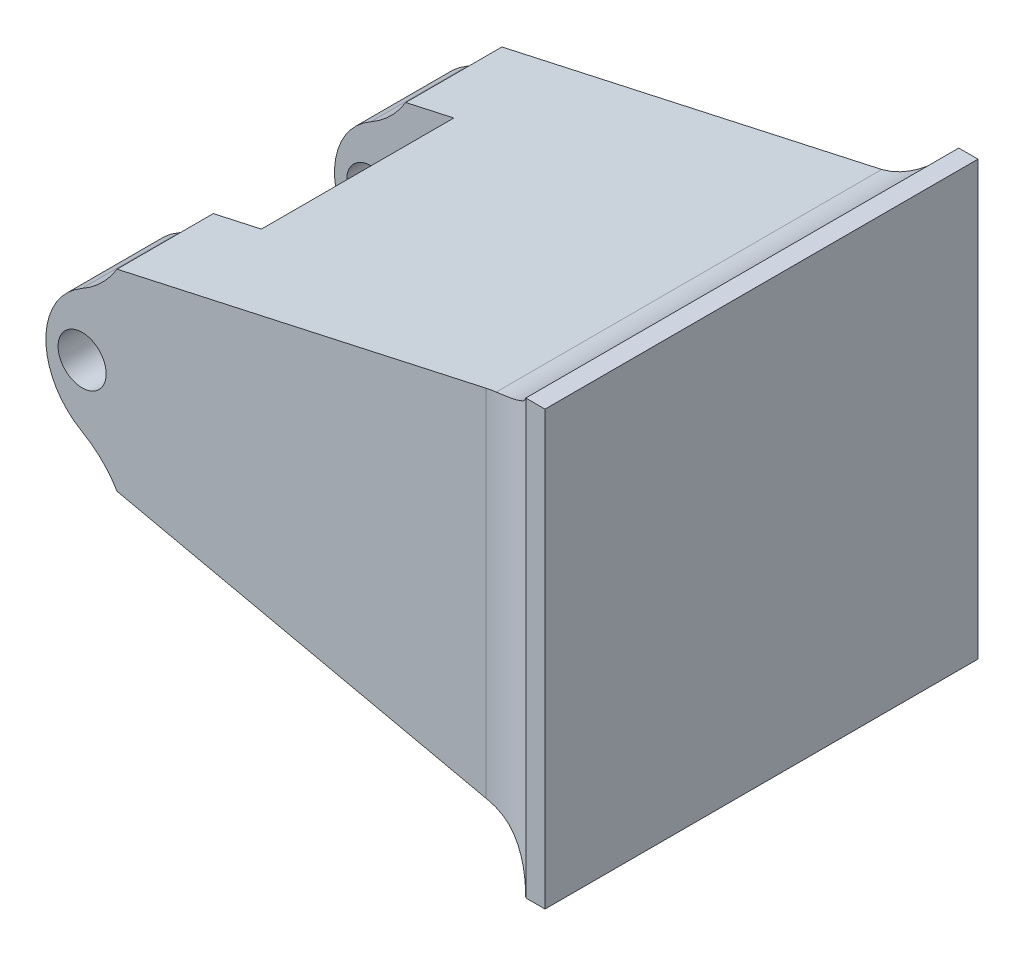
SolidWorks part; units mm, degrees
ref_plane "Front Plane" through (0, 0, 0) normal (0, 0, 1) x (1, 0, 0)
ref_plane "Top Plane" through (0, 0, 0) normal (0, 1, 0) x (1, 0, 0)
ref_plane "Right Plane" through (0, 0, 0) normal (1, 0, 0) x (0, 0, -1)
sketch "Sketch1" plane through (0, 0, 0) normal (0, 0, 1) x (1, 0, 0)
  line L0 (0, 0) -> (45.3393, -10)
  line L1 (45.3393, -10) -> (45.3393, 30)
  line L2 (0, 20) -> (45.3393, 30)
  line L3 (0, 0) -> (0, 20)
  dimension "D1" = 40
  dimension "D2" = 20
extrude "Boss-Extrude1" add sketch "Sketch1" along normal blind 20 and the other way blind 20 contours L2 L1 L0 L3
sketch "Sketch2" plane through (45.3393, 0, 0) normal (1, 0, 0) x (0, 0, -1)
  line L1 (-22.8606, 32.5) -> (22.1394, 32.5)
  line L2 (-22.8606, 32.5) -> (-22.8606, -12.5)
  line L3 (-22.8606, -12.5) -> (22.1394, -12.5)
  line L4 (22.1394, 32.5) -> (22.1394, -12.5)
  line L5 (-22.8606, 32.5) -> (22.1394, -12.5) construction
  line L6 (-22.8606, -12.5) -> (22.1394, 32.5) construction
  line L7 (20, 30) -> (-20, 30) construction
  point P0 (-0.3606, 10)
  dimension "D1" = 45
  dimension "D2" = 45
  dimension "D3" = 20
extrude "Boss-Extrude2" add sketch "Sketch2" along normal blind 2
sketch "Sketch3" plane through (0, 0, 20) normal (0, 0, 1) x (1, 0, 0)
  line L0 (0, 0) -> (0, 20) construction
  line L1 (0, 17.4004) -> (0, 2.5996)
  arc A0 (0, 17.4004) -> (0, 2.5996) centre (0, 10) ccw
  circle A2 centre (-3.6319, 10) radius 2.5
  dimension "D1" = 5
  dimension "D2" = 0
extrude "Boss-Extrude3" add sketch "Sketch3" against normal blind 10
fillet "Fillet1" radius 10 2 edges at (0, 2.5996, 15) (0, 17.4004, 15)
fillet "Fillet2" radius 10 4 edges at (45.3393, -10, 0) (45.3393, 10, -20) (45.3393, 30, 0) (45.3393, 10, 20)
mirror "Mirror1" about plane through (0, 0, 0) normal (0, 0, 1) of "Fillet1", "Boss-Extrude3"
sketch "Sketch4" plane through (0, 0, 0) normal (-1, 0, 0) x (0, 0, 1)
  line L0 (-10, 20) -> (-10, 23.7855)
  line L2 (-10, 20) -> (-10, 0)
  line L4 (10, 20) -> (10, 0)
  line L6 (10, -3.7855) -> (10, 0)
  line L7 (-10, 23.7855) -> (10, 23.7855)
  line L8 (10, 23.7855) -> (10, 20)
  line L9 (-10, -3.7855) -> (10, -3.7855)
  line L10 (-10, 0) -> (-10, -3.7855)
  point P4 (0, 10)
extrude "Cut-Extrude1" cut sketch "Sketch4" against normal blind 5
